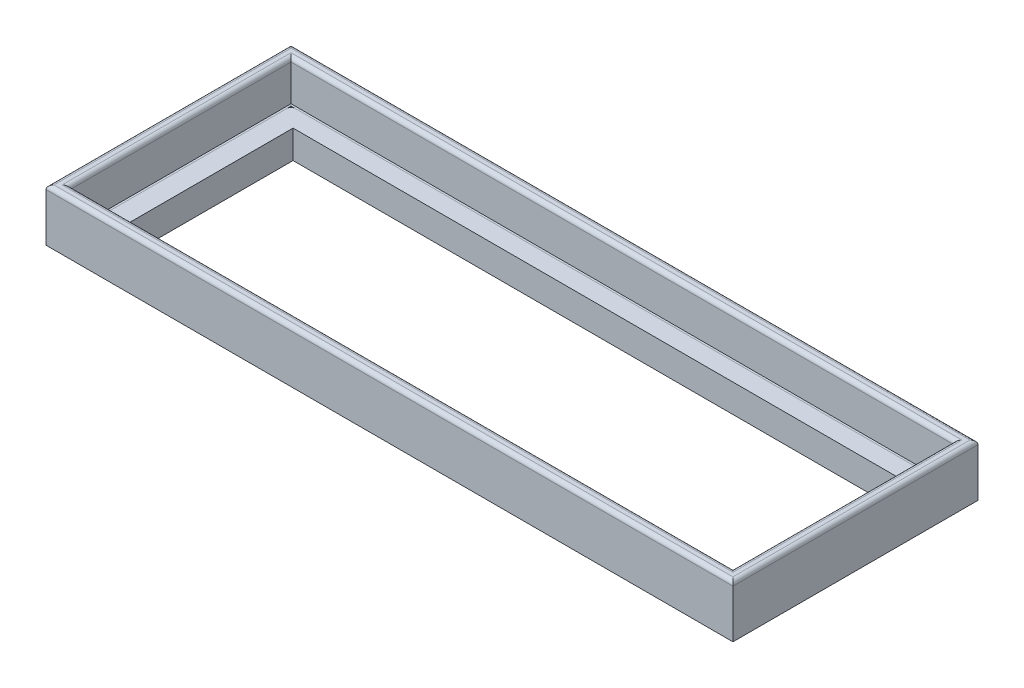
SolidWorks part; units mm, degrees
ref_plane "Front Plane" through (0, 0, 0) normal (0, 0, 1) x (1, 0, 0)
ref_plane "Top Plane" through (0, 0, 0) normal (0, 1, 0) x (1, 0, 0)
ref_plane "Right Plane" through (0, 0, 0) normal (1, 0, 0) x (0, 0, -1)
sketch "Sketch1" plane through (0, 0, 0) normal (0, 1, 0) x (1, 0, 0)
  line L0 (-85.5, 30.5) -> (85.5, 30.5)
  line L1 (-82.5, -27.5) -> (82.5, -27.5)
  line L2 (-82.5, -27.5) -> (-82.5, 27.5)
  line L3 (-82.5, 27.5) -> (82.5, 27.5)
  line L4 (82.5, -27.5) -> (82.5, 27.5)
  line L5 (-82.5, -27.5) -> (82.5, 27.5) construction
  line L6 (-82.5, 27.5) -> (82.5, -27.5) construction
  line L7 (85.5, -30.5) -> (85.5, 30.5)
  line L8 (-85.5, -30.5) -> (85.5, -30.5)
  line L9 (-85.5, -30.5) -> (-85.5, 30.5)
  line L10 (-82, 27) -> (82, 27)
  line L11 (82, -27) -> (82, 27)
  line L12 (-82, -27) -> (82, -27)
  line L13 (-82, -27) -> (-82, 27)
  point P0 (0, 0)
  dimension "D1" = 55
  dimension "D2" = 165
  dimension "D3" = 3
  dimension "D4" = 0.5
extrude "Boss-Extrude1" add sketch "Sketch1" along normal blind 10 contours L9 L8 L7 L0 L4 L1 L2 L3 region at (0, 0, -28.6845)
extrude "Boss-Extrude2" add sketch "Sketch1<5>" against normal blind 7 contours L10 L11 L12 L13
sketch "Sketch1<5>" plane through (0, 0, 0) normal (0, 1, 0) x (1, 0, 0) same geometry as "Sketch1"
extrude "Boss-Extrude3" add sketch "Sketch1<6>" against normal blind 3 contours L9 L8 L7 L0 L4 L1 L2 L3 | L1 L4 L3 L2 L12 L13 L10 L11 region at (0, 0, -28.6845) region at (-82.3261, 0, 0)
sketch "Sketch1<6>" plane through (0, 0, 0) normal (0, 1, 0) x (1, 0, 0) same geometry as "Sketch1"
fillet "Fillet1" radius 1 8 edges at (0, -7, 27) (82, -7, 0) (0, -7, -27) (-82, -7, 0) (82, -3.5, -27) (82, -3.5, 27) (0, 0, 27) (-82, -3.5, -27)
fillet "Fillet2" radius 1 8 edges at (0, 10, -27.5) (-82.5, 10, 0) (0, 10, 27.5) (82.5, 10, 0) (0, 10, -30.5) (85.5, 10, 0) (0, 10, 30.5) (-85.5, 10, 0)
sketch "Sketch2" plane through (0, 0, 0) normal (0, 1, 0) x (1, 0, 0)
  line L0 (-87.5, 37.5) -> (87.5, -37.5) construction
  line L1 (-77, -22.5) -> (77, -22.5)
  line L2 (-77, -22.5) -> (-77, 22.5)
  line L3 (-77, 22.5) -> (77, 22.5)
  line L4 (77, -22.5) -> (77, 22.5)
  line L5 (-77, -22.5) -> (77, 22.5) construction
  line L6 (-77, 22.5) -> (77, -22.5) construction
  line L7 (-82.5, 27.5) -> (82.5, 27.5) construction
  line L8 (-82, -27) -> (-82, 27) construction
  point P0 (0, 0)
  dimension "D1" = 5
  dimension "D2" = 5
extrude "Cut-Extrude1" cut sketch "Sketch2" against normal through all
